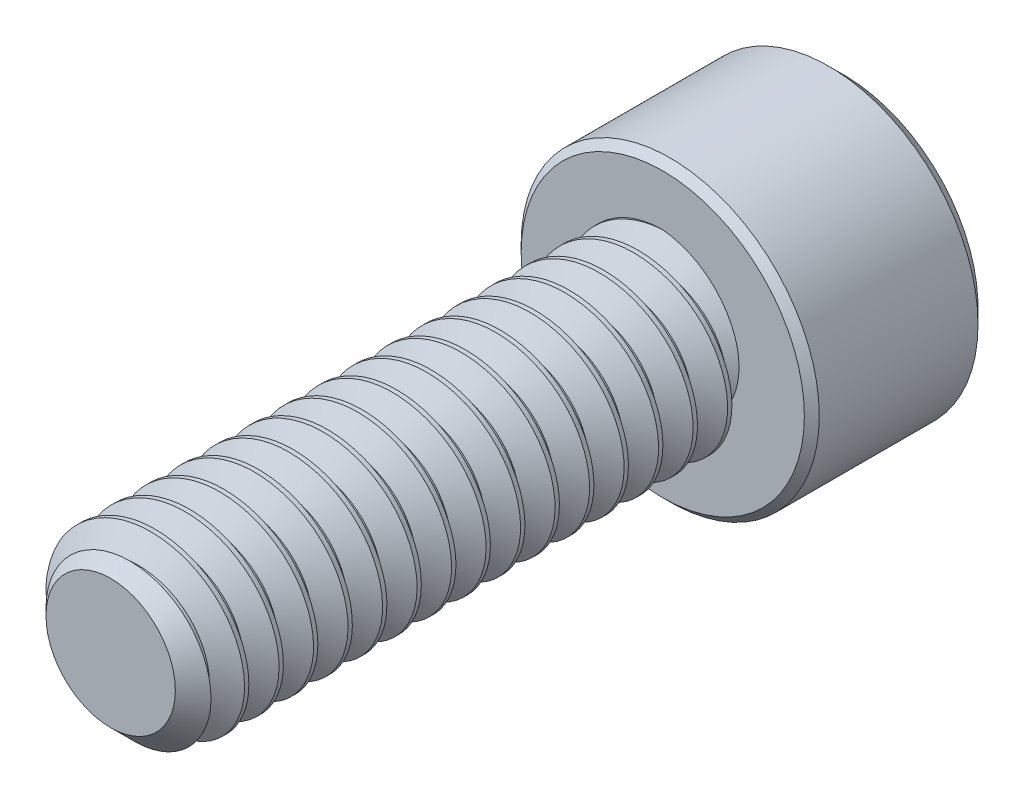
SolidWorks part; units mm, degrees
ref_plane "Front Plane" through (0, 0, 0) normal (0, 0, 1) x (1, 0, 0)
ref_plane "Top Plane" through (0, 0, 0) normal (0, 1, 0) x (1, 0, 0)
ref_plane "Right Plane" through (0, 0, 0) normal (1, 0, 0) x (0, 0, -1)
sketch "Sketch0" plane through (0, 0, 0) normal (1, 0, 0) x (0, 0, -1)
  line L0 (0, 0) -> (12.7, 0) construction
  point P2 (16.8656, 0)
  point P4 (0, 0)
  dimension "D1" = 12.7
  dimension "D2" = 4.1656
  dimension "Min Thread" = 0
sketch "Sketch1" plane through (0, 0, 0) normal (0, 0, 1) x (1, 0, 0)
  circle A0 centre (0, 0) radius 2.0828
  dimension "OD" = 4.1656
extrude "Extrude1" add sketch "Sketch1" against normal blind 12.7
sketch "Sketch2" plane through (0, 0, 0) normal (0, 0, 1) x (1, 0, 0)
  circle A0 centre (0, 0) radius 2.0828 construction
  circle A1 centre (0, 0) radius 2.0828
curve "Helix/Spiral1" pitch 0.7937 height 13.4937 turns 17 parameters "pitch"=0.7937
chamfer "Chamfer3" distance 0.5953 angle 45 1 edges at (2.0828, 0, 0)
sketch "Sketch3" plane through (0, 0, 0) normal (1, 0, 0) x (0, 0, -1)
  line L0 (-0.6945, 2.0828) -> (-0.3969, 1.5672)
  line L1 (-0.3969, 1.5672) -> (-0.2977, 1.5672)
  line L2 (-0.2977, 1.5672) -> (0, 2.0828)
  line L3 (-0.6945, 2.0828) -> (0, 2.0828)
  line L4 (-0.3473, 2.0828) -> (-0.3473, 1.5672) construction
  line L5 (-0.5457, 1.825) -> (-0.1488, 1.825) construction
  line L6 (0, 2.0828) -> (0, -2.0828) construction
  dimension "D1" = 0.0992
  dimension "D2" = 0.3969
  dimension "D3" = 60
sweep "Cut-Sweep1" cut profiles "Sketch3" path "Helix/Spiral1"
sketch "Sketch5" plane through (0, 0, 0) normal (1, 0, 0) x (0, 0, -1)
  line L0 (12.7, -1.5805) -> (12.7, 1.4861) construction
  line L1 (12.7, 2.0828) -> (0, 2.0828)
  line L2 (12.7, 2.0828) -> (12.7, 0)
  line L3 (12.7, 0) -> (-0.7581, 0)
  line L4 (0, 0) -> (12.7, 0) construction
  line L5 (0, 2.0828) -> (-0.7581, 0)
  line L6 (0, 0) -> (15.24, 0) construction
  dimension "D1" = 70
  dimension "D3" = 2.54
revolve "partially thread" [suppressed] add sketch "Sketch5" angle 360 about L6
sketch "Sketch6" plane through (0, 0, -12.7) normal (0, 0, -1) x (-1, 0, 0)
  circle A0 centre (0, 0) radius 3.429
  dimension "head dia" = 6.858
extrude "Extrude2" add sketch "Sketch6" along normal blind 4.1656
sketch "Sketch7" plane through (0, 0, -16.8656) normal (0, 0, -1) x (-1, 0, 0)
  line L1 (0, 2.0622) -> (-1.7859, 1.0311)
  line L2 (-1.7859, 1.0311) -> (-1.7859, -1.0311)
  line L3 (-1.7859, -1.0311) -> (0, -2.0622)
  line L4 (0, -2.0622) -> (1.7859, -1.0311)
  line L5 (1.7859, -1.0311) -> (1.7859, 1.0311)
  line L6 (1.7859, 1.0311) -> (0, 2.0622)
  circle A0 centre (0, 0) radius 1.7859 construction
  dimension "hex dia" = 3.5719
extrude "Cut-Extrude1" cut sketch "Sketch7" against normal blind 2.6789
sketch "Sketch8" plane through (0, 0, -16.8656) normal (0, 0, -1) x (-1, 0, 0)
  circle A0 centre (0, 0) radius 2.0622
extrude "Cut-Extrude2" cut sketch "Sketch8" against normal through all draft 45
chamfer "Chamfer1" distance 0.3429 angle 45 1 edges at (-3.429, 0, -16.8656)
chamfer "Chamfer2" distance 0.1715 angle 45 1 edges at (-3.429, 0, -12.7)
sketch "Sketch9" plane through (0, 0, 0) normal (1, 0, 0) x (0, 0, -1)
  line L0 (0, 2.0828) -> (0, -2.0828) construction
  line L1 (1.9844, 2.0828) -> (1.9844, -2.0828) construction
  line L2 (16.8656, 3.429) -> (16.8656, -3.429) construction
  line L3 (12.7, 3.429) -> (12.7, -3.429) construction
  line L4 (12.7, 3.2575) -> (12.7, -3.2575) construction
  line L5 (16.8656, -3.0861) -> (16.8656, 3.0861) construction
  line L6 (12.7, -3.429) -> (12.7, 3.429) construction
  line L7 (0, 1.4875) -> (0, -1.4875) construction
  line L8 (-0.6945, 2.0828) -> (0, 2.0828) construction
  line L9 (1.9844, 0) -> (0, 0) construction
  dimension "D1" = 1.9844
equation "\"D3@Helix/Spiral1\" = \"screw length@Extrude1\"+\"pitch@Helix/Spiral1\""
equation "\"D1@Sketch3\" = \"pitch@Helix/Spiral1\"*.125"
equation "\"D2@Sketch3\" = \"pitch@Helix/Spiral1\"*.5"
equation "\"D1@Cut-Extrude1\" = \"hex dia@Sketch7\"*.75"
equation "\"D1@Chamfer1\" = \"head dia@Sketch6\"*.05"
equation "\"D1@Sketch9\" = \"pitch@Helix/Spiral1\"*2.50"
equation "\"D1@Chamfer2\" = \"D1@Chamfer1\"/2"
equation "\"D1@Chamfer3\" = \"pitch@Helix/Spiral1\"*.750"
equation "\"D1@Sketch0\" = \"screw length@Extrude1\""
equation "\"D2@Sketch0\" = \"head depth@Extrude2\""
